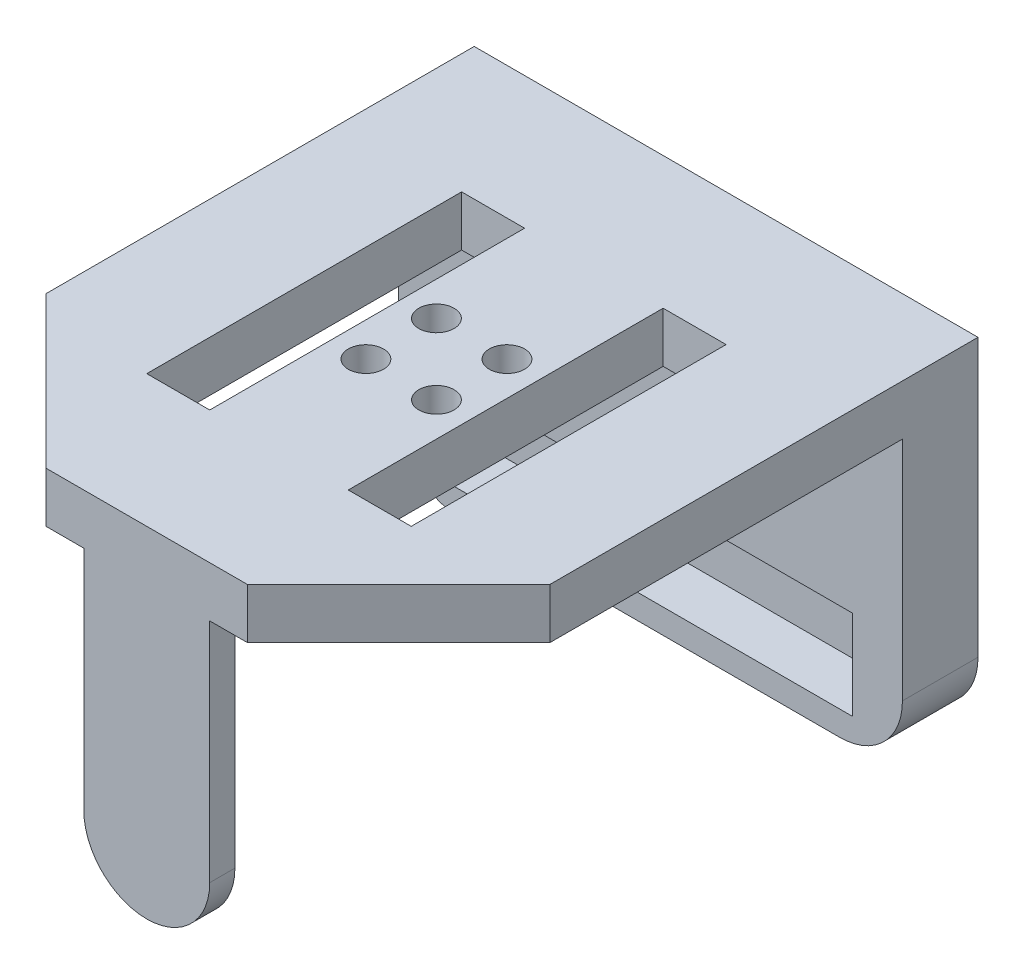
SolidWorks part; units mm, degrees
ref_plane "Front Plane" through (0, 0, 0) normal (0, 0, 1) x (1, 0, 0)
ref_plane "Top Plane" through (0, 0, 0) normal (0, 1, 0) x (1, 0, 0)
ref_plane "Right Plane" through (0, 0, 0) normal (1, 0, 0) x (0, 0, -1)
sketch "Schizzo3" plane through (0, 0, 0) normal (0, 0, 1) x (1, 0, 0)
  line L6 (-20, -13.5) -> (20, -13.5)
  line L13 (-20, -13.5) -> (-20, 13.5)
  line L14 (-20, 13.5) -> (20, 13.5)
  line L15 (20, -13.5) -> (20, 13.5)
  line L16 (-20, -13.5) -> (20, 13.5) construction
  line L17 (-20, 13.5) -> (20, -13.5) construction
  point P0 (0, 0)
  point P1 (0, 0)
  dimension "D1" = 40
  dimension "D2" = 27
extrude "Estrusione-Estrusione1" add sketch "Schizzo3" along normal blind 6
sketch "Schizzo4" plane through (0, 0, 6) normal (0, 0, 1) x (1, 0, 0)
  line L1 (-16.05, -4.45) -> (16.05, -4.45)
  line L2 (-16.05, -4.45) -> (-16.05, -11.55)
  line L3 (-16.05, -11.55) -> (16.05, -11.55)
  line L4 (16.05, -4.45) -> (16.05, -11.55)
  line L5 (-16.05, -4.45) -> (16.05, -11.55) construction
  line L6 (-16.05, -11.55) -> (16.05, -4.45) construction
  point P0 (0, -8)
  point P5 (0, 0)
  dimension "D1" = 32.1
  dimension "D2" = 7.1
  dimension "D3" = 8
extrude "Taglio-Estrusione1" cut sketch "Schizzo4" against normal blind 4
sketch "Schizzo5" plane through (0, 0, 2) normal (0, 0, 1) x (1, 0, 0)
  line L0 (-16.05, -4.45) -> (-16.05, -11.55) construction
  circle A0 centre (0, -8) radius 1.05
  point P2 (0, 0)
  point P6 (-16.05, -8)
  dimension "D1" = 2.1
extrude "Taglio-Estrusione2" cut sketch "Schizzo5" against normal through all
sketch "Schizzo6" plane through (0, 0, 6) normal (0, 0, 1) x (1, 0, 0)
  line L0 (20, -13.5) -> (20, 13.5) construction
  line L1 (-20, 13.5) -> (20, 13.5)
  line L2 (-20, 13.5) -> (-20, 9.5)
  line L3 (-20, 9.5) -> (20, 9.5)
  line L4 (20, 13.5) -> (20, 9.5)
  line L5 (-20, 13.5) -> (-20, -13.5) construction
  dimension "D1" = 4
extrude "Estrusione-Estrusione2" add sketch "Schizzo6" along normal blind 40 contours L2 L1 L4 L3
sketch "Schizzo7" plane through (0, 9.5, 0) normal (0, -1, 0) x (1, 0, 0)
  line L0 (-20, 46) -> (20, 46) construction
  line L1 (-5, 46) -> (5, 46)
  line L2 (-5, 46) -> (-5, 44)
  line L3 (-5, 44) -> (5, 44)
  line L4 (5, 46) -> (5, 44)
  point P6 (0, 46)
  point P7 (0, 44)
  dimension "D1" = 10
  dimension "D2" = 2
extrude "Estrusione-Estrusione3" add sketch "Schizzo7" along normal blind 23
sketch "Schizzo8" plane through (0, 13.5, 0) normal (0, 1, 0) x (1, 0, 0)
  line L0 (0, 0) -> (0, -46) construction
  line L1 (-20, -46) -> (20, -46) construction
  line L2 (-20, -23) -> (20, -23) construction
  line L3 (-20, -46) -> (-20, 0) construction
  line L4 (20, -46) -> (20, 0) construction
  line L5 (10.5, -10.5) -> (5.5, -10.5)
  line L6 (-10.5, -35.5) -> (-5.5, -35.5)
  line L7 (-10.5, -35.5) -> (-10.5, -10.5)
  line L8 (-10.5, -10.5) -> (-5.5, -10.5)
  line L9 (-5.5, -35.5) -> (-5.5, -10.5)
  line L10 (-10.5, -35.5) -> (-5.5, -10.5) construction
  line L11 (-10.5, -10.5) -> (-5.5, -35.5) construction
  line L12 (5.5, -35.5) -> (5.5, -10.5)
  line L13 (10.5, -35.5) -> (5.5, -35.5)
  line L14 (10.5, -35.5) -> (10.5, -10.5)
  line L15 (-20, -34) -> (-8, -46)
  line L16 (-8, -46) -> (-20, -46)
  line L17 (-20, -46) -> (-20, -34)
  line L18 (8, -46) -> (20, -46)
  line L19 (20, -34) -> (8, -46)
  line L20 (20, -46) -> (20, -34)
  circle A0 centre (-2.8, -20.2) radius 1.4
  circle A1 centre (-2.8, -25.8) radius 1.4
  circle A2 centre (2.8, -25.8) radius 1.4
  circle A3 centre (2.8, -20.2) radius 1.4
  point P19 (-8, -23)
  dimension "D1" = 2.8
  dimension "D2" = 2.8
  dimension "D3" = 2.8
  dimension "D4" = 5
  dimension "D5" = 25
  dimension "D6" = 8
  dimension "D7" = 12
  dimension "D8" = 12
extrude "Taglio-Estrusione3" cut sketch "Schizzo8" against normal through all
fillet "Raccordo1" radius 5 4 edges at (-5, -13.5, 45) (5, -13.5, 45) (20, -13.5, 3) (-20, -13.5, 3)
